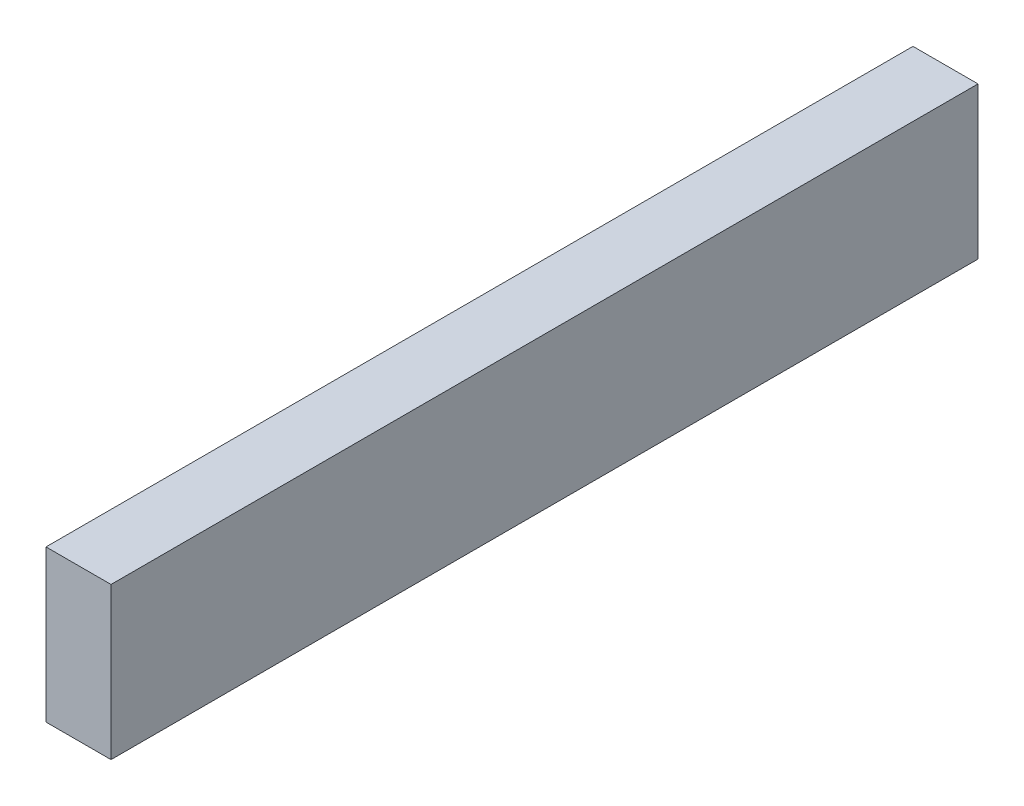
SolidWorks part; units mm, degrees
ref_plane "Front Plane" through (0, 0, 0) normal (0, 0, 1) x (1, 0, 0)
ref_plane "Top Plane" through (0, 0, 0) normal (0, 1, 0) x (1, 0, 0)
ref_plane "Right Plane" through (0, 0, 0) normal (1, 0, 0) x (0, 0, -1)
sketch "Sketch1" plane through (0, 0, 0) normal (0, 0, 1) x (1, 0, 0)
  line L1 (19.05, -44.45) -> (-19.05, -44.45)
  line L2 (19.05, -44.45) -> (19.05, 44.45)
  line L3 (19.05, 44.45) -> (-19.05, 44.45)
  line L4 (-19.05, -44.45) -> (-19.05, 44.45)
  line L5 (19.05, -44.45) -> (-19.05, 44.45) construction
  line L6 (19.05, 44.45) -> (-19.05, -44.45) construction
  point P0 (0, 0)
  dimension "D1" = 38.1
  dimension "D2" = 88.9
extrude "Boss-Extrude1" add sketch "Sketch1" along normal mid plane 508
